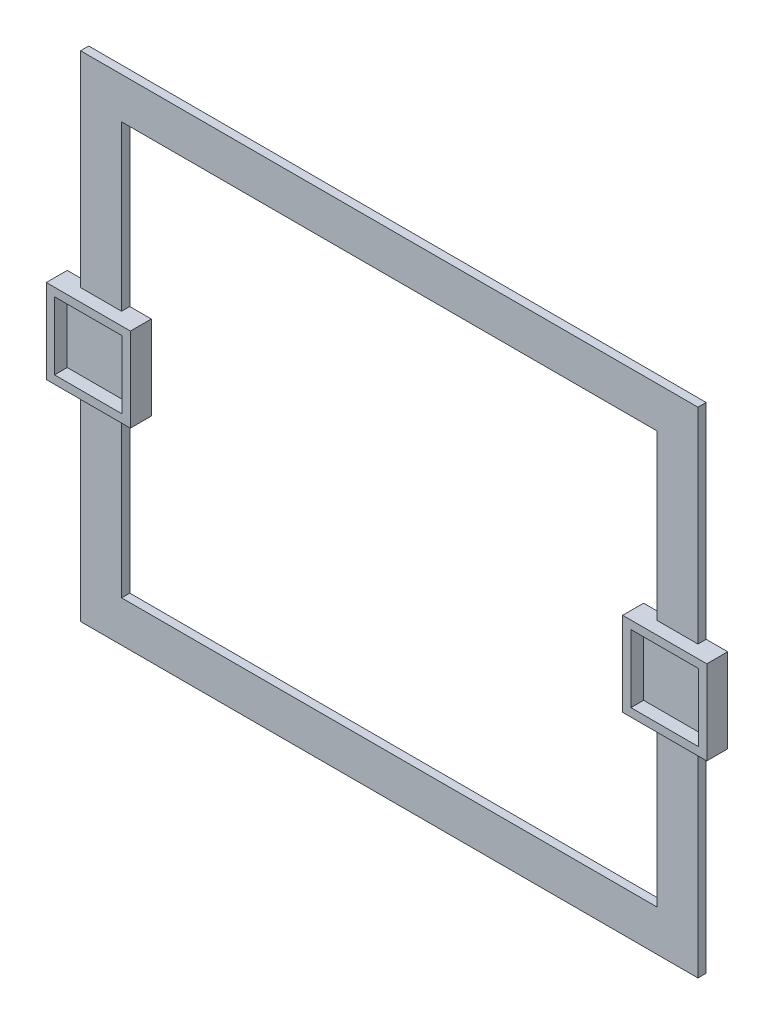
SolidWorks part; units mm, degrees
ref_plane "Front Plane" through (0, 0, 0) normal (0, 0, 1) x (1, 0, 0)
ref_plane "Top Plane" through (0, 0, 0) normal (0, 1, 0) x (1, 0, 0)
ref_plane "Right Plane" through (0, 0, 0) normal (1, 0, 0) x (0, 0, -1)
sketch "Sketch1" plane through (0, 0, 0) normal (0, 0, 1) x (1, 0, 0)
  line L1 (0, 0) -> (41.91, 0)
  line L2 (0, 0) -> (0, 41.91)
  line L3 (0, 41.91) -> (41.91, 41.91)
  line L4 (41.91, 0) -> (41.91, 41.91)
  line L5 (-5.08, 46.99) -> (46.99, 46.99)
  line L6 (-5.08, 46.99) -> (-5.08, -5.08)
  line L7 (-5.08, -5.08) -> (46.99, -5.08)
  line L8 (46.99, 46.99) -> (46.99, -5.08)
  line L9 (356.87, 41.91) -> (398.78, 41.91)
  line L10 (356.87, 41.91) -> (356.87, 0)
  line L11 (356.87, 0) -> (398.78, 0)
  line L12 (398.78, 41.91) -> (398.78, 0)
  line L13 (351.79, 46.99) -> (403.86, 46.99)
  line L14 (351.79, 46.99) -> (351.79, -5.08)
  line L15 (351.79, -5.08) -> (403.86, -5.08)
  line L16 (403.86, 46.99) -> (403.86, -5.08)
  point P17 (356.87, 20.955)
  dimension "D1" = 41.91
  dimension "D2" = 41.91
  dimension "D3" = 5.08
  dimension "D4" = 5.08
  dimension "D5" = 5.08
  dimension "D6" = 5.08
  dimension "D7" = 41.91
  dimension "D8" = 41.91
  dimension "D9" = 5.08
  dimension "D10" = 5.08
  dimension "D11" = 304.8
extrude "Boss-Extrude1" add sketch "Sketch1" along normal blind 7.874
sketch "Sketch2" plane through (0, 0, 0) normal (0, 0, -1) x (-1, 0, 0)
  line L0 (-46.99, 46.99) -> (5.08, 46.99) construction
  line L10 (-8.255, -5.08) -> (-8.255, -132.08)
  line L11 (-8.255, -132.08) -> (-33.655, -132.08)
  line L12 (-33.655, -5.08) -> (-33.655, -106.68)
  line L14 (-365.125, -5.08) -> (-365.125, -106.68)
  line L15 (-365.125, -132.08) -> (-390.525, -132.08)
  line L16 (-390.525, -5.08) -> (-390.525, -132.08)
  line L25 (-33.655, -132.08) -> (-365.125, -132.08)
  line L27 (-33.655, -106.68) -> (-365.125, -106.68)
  line L34 (-8.255, 46.99) -> (-8.255, 173.99)
  line L35 (-8.255, 173.99) -> (-33.655, 173.99)
  line L37 (-403.86, 46.99) -> (-351.79, 46.99) construction
  line L40 (-365.125, 173.99) -> (-390.525, 173.99)
  line L41 (-390.525, 46.99) -> (-390.525, 173.99)
  line L54 (-33.655, 173.99) -> (-365.125, 173.99)
  line L55 (-33.655, 46.99) -> (-33.655, 148.59)
  line L56 (-33.655, 148.59) -> (-33.655, 46.99)
  line L57 (-365.125, 46.99) -> (-365.125, 148.59)
  line L58 (-365.125, 148.59) -> (-33.655, 148.59)
  line L59 (-365.125, 46.99) -> (-390.525, 46.99)
  line L60 (-365.125, -5.08) -> (-390.525, -5.08)
  line L61 (-8.255, 46.99) -> (-33.655, 46.99)
  line L62 (-8.255, -5.08) -> (-33.655, -5.08)
  line L63 (5.08, -5.08) -> (-46.99, -5.08) construction
  line M48 (5.08, 46.99) -> (-46.99, 46.99)
  line M50 (-46.99, -5.08) -> (5.08, -5.08)
  dimension "D1" = 127
  dimension "D2" = 25.4
  dimension "D3" = 127
  dimension "D4" = 25.4
  dimension "D5" = 127
  dimension "D6" = 101.6
  dimension "D7" = 0
  dimension "D8" = 25.4
  dimension "D9" = 127
extrude "Boss-Extrude3" add sketch "Sketch2" along normal blind 5.08 separate body contours L59 L57 L58 L55 L34 L35 L54 L40 L41 M48 | L14 L60 L16 L15 L25 L11 L10 L12 L27 M50 region at (12.2831, -68.58, 0) region at (20.955, 51.0181, 0)
sketch "Sketch3" plane through (0, 0, 0) normal (0, 0, -1) x (-1, 0, 0)
  line L1 (5.08, -5.08) -> (-46.99, -5.08)
  line L2 (5.08, -5.08) -> (5.08, 46.99)
  line L3 (5.08, 46.99) -> (-46.99, 46.99)
  line L4 (-46.99, -5.08) -> (-46.99, 46.99)
  line L5 (-351.79, -5.08) -> (-403.86, -5.08)
  line L6 (-351.79, -5.08) -> (-351.79, 46.99)
  line L7 (-351.79, 46.99) -> (-403.86, 46.99)
  line L8 (-403.86, -5.08) -> (-403.86, 46.99)
extrude "Boss-Extrude4" add sketch "Sketch3" along normal blind 5.08
